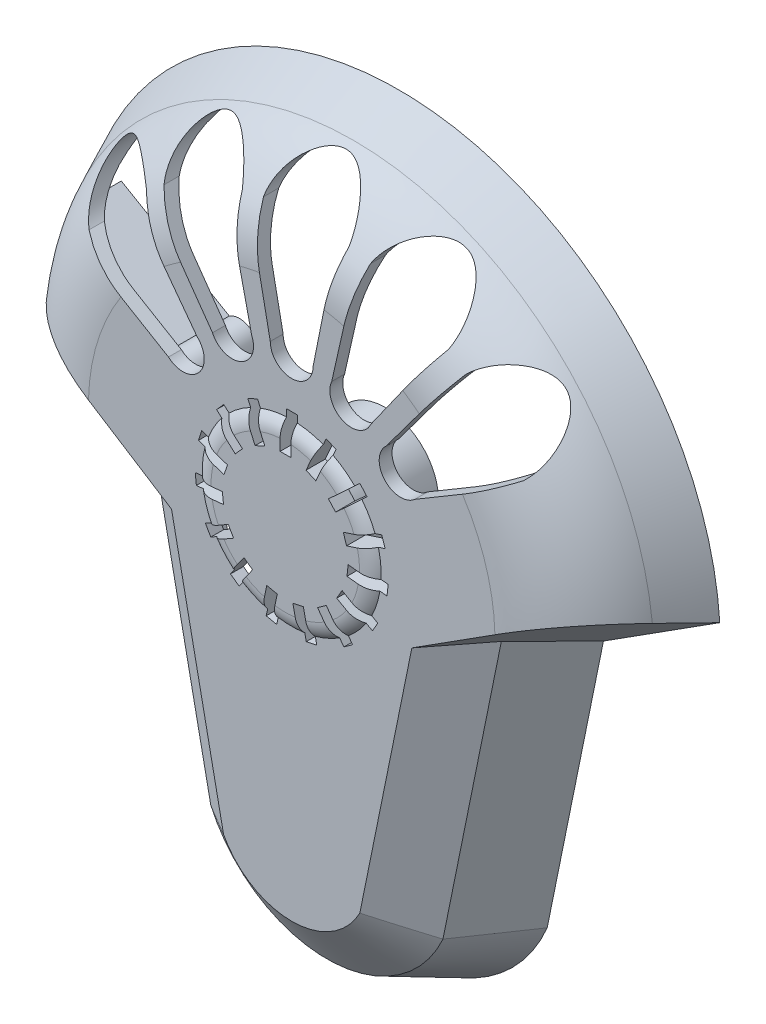
SolidWorks part; units mm, degrees
ref_plane "Front Plane" through (0, 0, 0) normal (0, 0, 1) x (1, 0, 0)
ref_plane "Top Plane" through (0, 0, 0) normal (0, 1, 0) x (1, 0, 0)
ref_plane "Right Plane" through (0, 0, 0) normal (1, 0, 0) x (0, 0, -1)
sketch "Sketch1" plane through (0, 0, 0) normal (0, 0, 1) x (1, 0, 0)
  line L0 (0, 0) -> (0, 88.332) construction
  line L1 (-17.574, -7.3523) -> (-24.2375, 25.4)
  line L2 (-24.2375, 25.4) -> (-38.0223, 34.1819)
  line L3 (24.2375, 25.4) -> (38.0223, 34.1819)
  line L4 (17.574, -7.3523) -> (24.2375, 25.4)
  arc A0 (-17.574, -7.3523) -> (17.574, -7.3523) centre (0, 0) ccw
  arc A1 (-38.0223, 34.1819) -> (38.0223, 34.1819) centre (0, 31.75) cw
  point P9 (0, 0)
  point P11 (0, -0.5751)
  point P12 (0, 0)
  point P13 (0, 0)
  dimension "D1" = 19.05
  dimension "D3" = 38.1
  dimension "D2" = 23
  dimension "D4" = 115
  dimension "D5" = 31.75
  dimension "D6" = 25.4
extrude "Boss-Extrude1" add sketch "Sketch1" along normal blind 12.7 draft 25
fillet "Fillet1" radius 12.7 1 edges at (0, 63.9279, 12.7)
chamfer "Chamfer1" distance 4.5974 angle 30 3 edges at (15.4165, 11.7475, 12.7) (-15.4165, 11.7475, 12.7) (0, -13.1279, 12.7) first distance on face at (17.4516, 10.6111, 7.9375) first distance on face at (-17.4516, 10.6111, 7.9375) first distance on face at (0, -10.819, 9.525)
shell "Shell2" thickness 1.524 removed face at (0, 21.4049, 0)
sketch "Sketch2" plane through (0, 0, 12.7) normal (0, 0, 1) x (1, 0, 0)
  line L0 (0, 31.75) -> (0, 74.2558) construction
  line L1 (-2.54, 49.1139) -> (-5.08, 61.8139)
  line L2 (2.54, 49.1139) -> (5.08, 61.8139)
  line L3 (9.3829, 46.5796) -> (16.8689, 57.1485)
  line L4 (4.7421, 48.6458) -> (7.5873, 61.281)
  line L5 (14.6035, 41.4811) -> (25.741, 48.0915)
  line L6 (11.2043, 45.2563) -> (18.9427, 55.6419)
  line L7 (0, 31.75) -> (0, 49.1139) construction
  line L8 (0, 31.75) -> (7.0625, 47.6127) construction
  line L9 (-11.2043, 45.2563) -> (-18.9427, 55.6419)
  line L10 (-14.6035, 41.4811) -> (-25.741, 48.0915)
  line L11 (-4.7421, 48.6458) -> (-7.5873, 61.281)
  line L12 (-9.3829, 46.5796) -> (-16.8689, 57.1485)
  arc A0 (-2.54, 49.1139) -> (2.54, 49.1139) centre (0, 49.1139) ccw
  arc A1 (-5.08, 61.8139) -> (5.08, 61.8139) centre (0, 61.8139) cw
  arc A2 (7.5873, 61.281) -> (16.8689, 57.1485) centre (12.2281, 59.2147) cw
  arc A3 (4.7421, 48.6458) -> (9.3829, 46.5796) centre (7.0625, 47.6127) ccw
  arc A4 (18.9427, 55.6419) -> (25.741, 48.0915) centre (22.3418, 51.8667) cw
  arc A5 (11.2043, 45.2563) -> (14.6035, 41.4811) centre (12.9039, 43.3687) ccw
  arc A6 (-11.2043, 45.2563) -> (-14.6035, 41.4811) centre (-12.9039, 43.3687) cw
  arc A7 (-18.9427, 55.6419) -> (-25.741, 48.0915) centre (-22.3418, 51.8667) ccw
  arc A8 (-4.7421, 48.6458) -> (-9.3829, 46.5796) centre (-7.0625, 47.6127) cw
  arc A9 (-7.5873, 61.281) -> (-16.8689, 57.1485) centre (-12.2281, 59.2147) ccw
  dimension "D1" = 2.54
  dimension "D2" = 5.08
  dimension "D3" = 12.7
  dimension "D4" = 17.3639
  dimension "D6" = 24
  dimension "D5" = 3
extrude "Cut-Extrude1" cut sketch "Sketch2" against normal through all
sketch "Sketch3" plane through (0, 0, 12.7) normal (0, 0, 1) x (1, 0, 0)
  circle A0 centre (0, 31.75) radius 10.6045
  dimension "D1" = 21.209
extrude "Boss-Extrude2" add sketch "Sketch3" along normal blind 0.762
fillet "Fillet2" radius 2.54 1 edges at (10.6045, 31.75, 13.462)
sketch "Sketch5" plane through (0, 0, 13.462) normal (0, 0, 1) x (1, 0, 0)
  line L0 (0, 31.75) -> (0, 51.079) construction
  line L6 (-0.6104, 43.1734) -> (0.6596, 43.1734)
  line L7 (0.6596, 43.1734) -> (0.6596, 39.1734)
  line L8 (0.6596, 39.1734) -> (-0.6104, 39.1734)
  line L9 (-0.6104, 39.1734) -> (-0.6104, 43.1734)
  line L10 (4.0887, 42.4341) -> (5.2489, 41.9175)
  line L11 (5.2489, 41.9175) -> (3.622, 38.2633)
  line L12 (3.622, 38.2633) -> (2.4618, 38.7799)
  line L13 (2.4618, 38.7799) -> (4.0887, 42.4341)
  line L14 (8.0808, 39.8473) -> (8.9306, 38.9035)
  line L15 (8.9306, 38.9035) -> (5.958, 36.227)
  line L16 (5.958, 36.227) -> (5.1082, 37.1708)
  line L17 (5.1082, 37.1708) -> (8.0808, 39.8473)
  line L18 (10.6757, 35.8605) -> (11.0681, 34.6527)
  line L19 (11.0681, 34.6527) -> (7.2639, 33.4166)
  line L20 (7.2639, 33.4166) -> (6.8715, 34.6245)
  line L21 (6.8715, 34.6245) -> (10.6757, 35.8605)
  line L22 (11.4246, 31.163) -> (11.2919, 29.8999)
  line L23 (11.2919, 29.8999) -> (7.3138, 30.318)
  line L24 (7.3138, 30.318) -> (7.4465, 31.5811)
  line L25 (7.4465, 31.5811) -> (11.4246, 31.163)
  line L26 (10.1981, 26.5669) -> (9.5631, 25.467)
  line L27 (9.5631, 25.467) -> (6.099, 27.467)
  line L28 (6.099, 27.467) -> (6.734, 28.5669)
  line L29 (6.734, 28.5669) -> (10.1981, 26.5669)
  line L30 (7.2083, 22.867) -> (6.1809, 22.1206)
  line L31 (6.1809, 22.1206) -> (3.8297, 25.3566)
  line L32 (3.8297, 25.3566) -> (4.8572, 26.1031)
  line L33 (4.8572, 26.1031) -> (7.2083, 22.867)
  line L34 (2.9721, 20.7031) -> (1.7298, 20.4391)
  line L35 (1.7298, 20.4391) -> (0.8982, 24.3517)
  line L36 (0.8982, 24.3517) -> (2.1404, 24.6157)
  line L37 (2.1404, 24.6157) -> (2.9721, 20.7031)
  line L38 (-1.778, 20.4493) -> (-3.0203, 20.7134)
  line L39 (-3.0203, 20.7134) -> (-2.1886, 24.626)
  line L40 (-2.1886, 24.626) -> (-0.9464, 24.3619)
  line L41 (-0.9464, 24.3619) -> (-1.778, 20.4493)
  line L42 (-6.2207, 22.1495) -> (-7.2482, 22.896)
  line L43 (-7.2482, 22.896) -> (-4.897, 26.1321)
  line L44 (-4.897, 26.1321) -> (-3.8696, 25.3856)
  line L45 (-3.8696, 25.3856) -> (-6.2207, 22.1495)
  line L46 (-9.5878, 25.5097) -> (-10.2228, 26.6096)
  line L47 (-10.2228, 26.6096) -> (-6.7587, 28.6096)
  line L48 (-6.7587, 28.6096) -> (-6.1237, 27.5097)
  line L49 (-6.1237, 27.5097) -> (-9.5878, 25.5097)
  line L50 (-11.297, 29.9489) -> (-11.4298, 31.2119)
  line L51 (-11.4298, 31.2119) -> (-7.4517, 31.6301)
  line L52 (-7.4517, 31.6301) -> (-7.3189, 30.367)
  line L53 (-7.3189, 30.367) -> (-11.297, 29.9489)
  line L54 (-11.0529, 34.6995) -> (-10.6605, 35.9074)
  line L55 (-10.6605, 35.9074) -> (-6.8562, 34.6713)
  line L56 (-6.8562, 34.6713) -> (-7.2487, 33.4635)
  line L57 (-7.2487, 33.4635) -> (-11.0529, 34.6995)
  line L58 (-8.8977, 38.9402) -> (-8.0479, 39.8839)
  line L59 (-8.0479, 39.8839) -> (-5.0753, 37.2074)
  line L60 (-5.0753, 37.2074) -> (-5.9251, 36.2636)
  line L61 (-5.9251, 36.2636) -> (-8.8977, 38.9402)
  line L62 (-5.2039, 41.9375) -> (-4.0437, 42.4541)
  line L63 (-4.0437, 42.4541) -> (-2.4168, 38.7999)
  line L64 (-2.4168, 38.7999) -> (-3.577, 38.2834)
  line L65 (-3.577, 38.2834) -> (-5.2039, 41.9375)
  line L66 (0, 31.75) -> (-0.6104, 39.1734) construction
  line L67 (0, 31.75) -> (2.4618, 38.7799) construction
  point P4 (0.6596, 41.1734)
  dimension "D1" = 4
  dimension "D2" = 1.27
  dimension "D3" = 9.4234
  dimension "D5" = 24
  dimension "D6" = 7.4485
  dimension "D4" = 15
extrude "Cut-Extrude2" cut sketch "Sketch5" against normal through all
sketch "Sketch6" plane through (0, 0, 11.176) normal (0, 0, -1) x (-1, 0, 0)
  circle A0 centre (0, 31.75) radius 6.35
  circle A1 centre (0, 31.75) radius 5
  dimension "D1" = 12.7
  dimension "D2" = 10
extrude "Boss-Extrude3" add sketch "Sketch6" along normal blind 9.525
sketch "Sketch7" plane through (0, 0, 11.176) normal (0, 0, -1) x (-1, 0, 0)
  circle A0 centre (-16.8919, 36.378) radius 2.2225
  circle A1 centre (-16.8919, 36.378) radius 1.27
  dimension "D1" = 4.445
  dimension "D2" = 2.54
extrude "Boss-Extrude4" add sketch "Sketch7" along normal blind 9.525
sketch "Sketch8" plane through (0, 0, 1.651) normal (0, 0, -1) x (-1, 0, 0)
  line L0 (-16.8919, 36.378) -> (-16.8919, 45.6759) construction
  line L1 (-16.8919, 36.378) -> (-35.1375, 36.378) construction
  line L2 (-19.1144, 36.378) -> (-18.4231, 37.9889)
  line L3 (-18.4231, 37.9889) -> (-32.9665, 42.3224)
  line L4 (-32.9665, 42.3224) -> (-33.441, 40.73)
  line L5 (-33.441, 40.73) -> (-19.1144, 36.378)
  line L6 (-16.8919, 34.1555) -> (-18.8394, 35.3072)
  line L7 (-18.8394, 35.3072) -> (-26.2777, 28.2512)
  line L8 (-26.2777, 28.2512) -> (-24.2505, 27.0525)
  line L9 (-24.2505, 27.0525) -> (-16.8919, 34.1555)
  circle A0 centre (-16.8919, 36.378) radius 2.2225 construction
  circle A1 centre (-16.8919, 36.378) radius 2.2225 construction
extrude "Boss-Extrude6" add sketch "Sketch8" against normal up to next
sketch "Sketch9" plane through (0, 0, 1.651) normal (0, 0, -1) x (-1, 0, 0)
  line L0 (0, 0) -> (0, 75.7283) construction
sketch "Sketch10" plane through (0, 0, 11.176) normal (0, 0, -1) x (-1, 0, 0)
  line L0 (-16.8919, 36.378) -> (22.3071, 36.378) construction
  circle A0 centre (17.2457, 36.378) radius 2.2225
  circle A2 centre (17.2457, 36.378) radius 1.27
  dimension "D1" = 4.445
  dimension "D2" = 2.54
extrude "Boss-Extrude8" add sketch "Sketch10" along normal blind 9.525
sketch "Sketch11" plane through (0, 0, 1.651) normal (0, 0, -1) x (-1, 0, 0)
  line L0 (18.4444, 38.2496) -> (31.2451, 45.6956)
  line L1 (31.2451, 45.6956) -> (31.802, 44.374)
  line L2 (31.802, 44.374) -> (19.3391, 37.1245)
  line L3 (19.3391, 37.1245) -> (18.4444, 38.2496)
  line L4 (17.7977, 34.2252) -> (23.8713, 28.1516)
  line L5 (23.8713, 28.1516) -> (25.7122, 29.9926)
  line L6 (25.7122, 29.9926) -> (19.4682, 36.378)
  line L7 (19.4682, 36.378) -> (17.7977, 34.2252)
  circle A0 centre (17.2457, 36.378) radius 2.2225 construction
  arc A1 (33.9282, 36.1788) -> (27.4087, 52.2316) centre (0, 31.75) ccw construction
  circle A2 centre (17.2457, 36.378) radius 2.2225 construction
extrude "Boss-Extrude9" add sketch "Sketch11" against normal up to next
sketch "Sketch12" plane through (0, 0, 11.176) normal (0, 0, -1) x (-1, 0, 0)
  circle A0 centre (0, 0) radius 2.2225
  circle A1 centre (0, 0) radius 1.27
  dimension "D1" = 4.445
  dimension "D2" = 2.54
extrude "Boss-Extrude10" add sketch "Sketch12" along normal blind 9.525
sketch "Sketch14" plane through (0, 0, 1.651) normal (0, 0, -1) x (-1, 0, 0)
  line L0 (0.9759, -1.9968) -> (1.1513, -1.901)
  circle A0 centre (0, 0) radius 2.2225 construction
